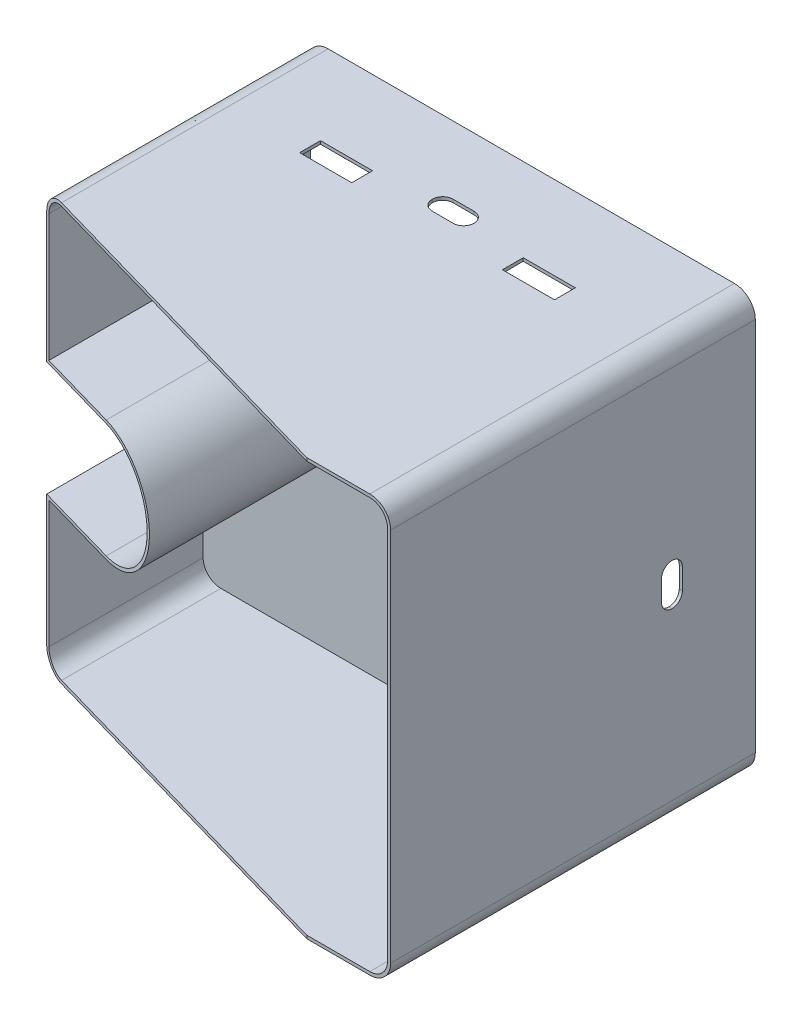
SolidWorks part; units mm, degrees
ref_plane "前视基准面" through (0, 0, 0) normal (0, 0, 1) x (1, 0, 0)
ref_plane "上视基准面" through (0, 0, 0) normal (0, 1, 0) x (1, 0, 0)
ref_plane "右视基准面" through (0, 0, 0) normal (1, 0, 0) x (0, 0, -1)
other "Configuration Table"
sketch "草图1" plane through (0, 0, 0) normal (0, 0, 1) x (1, 0, 0)
  line L0 (-135, 55) -> (-215, 55)
  line L1 (-195, -200) -> (195, -200)
  line L2 (-215, -180) -> (-215, -55)
  line L3 (-195, 200) -> (195, 200)
  line L4 (215, -180) -> (215, 180)
  line L5 (-215, -200) -> (215, 200) construction
  line L6 (-215, 200) -> (215, -200) construction
  line L7 (-135, -55) -> (-215, -55)
  line L8 (-215, 55) -> (-215, 180)
  line L9 (0, 0) -> (-50000, 0) construction
  arc A0 (-135, -55) -> (-135, 55) centre (-135, 0) ccw
  arc A1 (195, -200) -> (215, -180) centre (195, -180) ccw
  arc A2 (-195, -200) -> (-215, -180) centre (-195, -180) cw
  arc A3 (-215, 180) -> (-195, 200) centre (-195, 180) cw
  arc A4 (195, 200) -> (215, 180) centre (195, 180) cw
  point P0 (0, 0)
  dimension "D3" = 110
  dimension "D4" = 20
  dimension "D1" = 430
  dimension "D2" = 400
  dimension "D5" = 80
extrude "凸台-拉伸1" add sketch "草图1" along normal blind 250
shell "抽壳1" thickness 3 removed face at (-53.75, 0, 250)
sketch "草图3" plane through (0, 200, 0) normal (0, 1, 0) x (1, 0, 0)
  line L0 (134.4738, -250) -> (-215.5262, -150)
  line L1 (195, -250) -> (-195, -250) construction
  line L2 (-215.5262, -150) -> (-215.5262, -250)
  line L3 (-215.5262, -250) -> (134.4738, -250)
  dimension "D1" = 350
  dimension "D2" = 100
extrude "切除-拉伸1" cut sketch "草图3" against normal blind 547
sketch "草图4" plane through (0, 0, 0) normal (0, 0, -1) x (-1, 0, 0)
  line L2 (0.0199, 0) -> (50000.0199, 0) construction
  line L5 (195, -200) -> (-195, -200)
  line L6 (215, -180) -> (215, 180)
  line L8 (-215, -180) -> (-215, 180)
  line L9 (195, 200) -> (-195, 200)
  line L10 (215, -200) -> (-215, 200) construction
  line L11 (-215, -200) -> (215, 200) construction
  line L12 (195, -197) -> (-195, -197)
  line L13 (-212, -180) -> (-212, 180)
  line L14 (195, 197) -> (-195, 197)
  line L15 (212, -180) -> (212, 180)
  line L16 (212.9567, -202.1966) -> (-217.0433, 197.8034)
  line L17 (-217.0433, -197.8034) -> (212.9567, 202.1966)
  arc A0 (215, 180) -> (195, 200) centre (195, 180) ccw
  arc A1 (-215, 180) -> (-195, 200) centre (-195, 180) cw
  arc A5 (-195, -200) -> (-215, -180) centre (-195, -180) cw
  arc A6 (215, -180) -> (195, -200) centre (195, -180) cw
  arc A7 (-195, -197) -> (-212, -180) centre (-195, -180) cw
  arc A8 (-212, 180) -> (-195, 197) centre (-195, 180) cw
  arc A9 (212, 180) -> (195, 197) centre (195, 180) ccw
  arc A10 (212, -180) -> (195, -197) centre (195, -180) cw
  point P0 (0, 0)
  point P1 (0, 0)
  dimension "D3" = 20
  dimension "D1" = 430
  dimension "D2" = 400
  dimension "D4" = 3
extrude "凸台-拉伸3" add sketch "草图4" along normal blind 100 contours L9 A1 L8 A5 L5 A6 L6 A0 | L14 A8 L13 A7 L12 A10 L15 A9
sketch "草图6" plane through (0, 200, 0) normal (0, 1, 0) x (1, 0, 0)
  line L0 (-195, 100) -> (195, 100) construction
  line L1 (-122.3772, 0) -> (-72.3772, 0)
  line L2 (-122.3772, 0) -> (-122.3772, 20)
  line L3 (-122.3772, 20) -> (-72.3772, 20)
  line L4 (-72.3772, 0) -> (-72.3772, 20)
  line L5 (72.2462, 0) -> (122.2462, 0)
  line L6 (72.2462, 0) -> (72.2462, 20)
  line L7 (72.2462, 20) -> (122.2462, 20)
  line L8 (122.2462, 0) -> (122.2462, 20)
  line L9 (-215, -150.1503) -> (-215, 100) construction
  dimension "D1" = 50
  dimension "D2" = 20
  dimension "D3" = 50
  dimension "D4" = 20
  dimension "D5" = 80
  dimension "D6" = 80
  dimension "D7" = 20
  dimension "D8" = 92.6228
  dimension "D9" = 144.6234
extrude "切除-拉伸3" cut sketch "草图6" against normal blind 472
sketch "草图7" plane through (-215, 0, 0) normal (-1, 0, 0) x (0, 0, 1)
  line L0 (-10, 19.649) -> (-10, -20.351)
  line L4 (-30, 19.649) -> (-30, -20.351)
  line L5 (-10, -20.351) -> (-30, -20.351)
  line L6 (-10, 19.649) -> (-30, 19.649)
  line L7 (0, -55) -> (0, 55) construction
  point P0 (0, 0)
  dimension "D1" = 40
  dimension "D2" = 20
  dimension "D3" = 10
extrude "切除-拉伸4" cut sketch "草图7" against normal blind 472
fillet "圆角1" radius 10 4 edges at (-213.5, -20.351, -30) (-213.5, -20.351, -10) (-213.5, 19.649, -10) (-213.5, 19.649, -30)
fillet "圆角2" radius 10 4 edges at (213.5, -20.351, -30) (213.5, 19.649, -30) (213.5, 19.649, -10) (213.5, -20.351, -10)
sketch "草图8" plane through (0, 200, 0) normal (0, 1, 0) x (1, 0, 0)
  line L0 (0, 0) -> (0, 50000) construction
  line L1 (10.1, 15) -> (-10.1, 15)
  line L2 (20, 24.9) -> (20, 25.1)
  line L3 (10.1, 35) -> (-10.1, 35)
  line L4 (-20, 24.9) -> (-20, 25.1)
  line L5 (20, 15) -> (-20, 35) construction
  line L6 (20, 35) -> (-20, 15) construction
  line L7 (-195, 100) -> (195, 100) construction
  arc A0 (20, 25.1) -> (10.1, 35) centre (10.1, 25.1) ccw
  arc A1 (-10.1, 15) -> (-20, 24.9) centre (-10.1, 24.9) cw
  arc A2 (10.1, 15) -> (20, 24.9) centre (10.1, 24.9) ccw
  arc A3 (-10.1, 35) -> (-20, 25.1) centre (-10.1, 25.1) ccw
  point P0 (0, 25)
  point P20 (0, 26.5451)
  point P21 (0, 18.5484)
  point P22 (0, 20.5986)
  dimension "D3" = 9.9
  dimension "D1" = 40
  dimension "D2" = 20
  dimension "D4" = 75
extrude "切除-拉伸5" cut sketch "草图8" against normal blind 472
